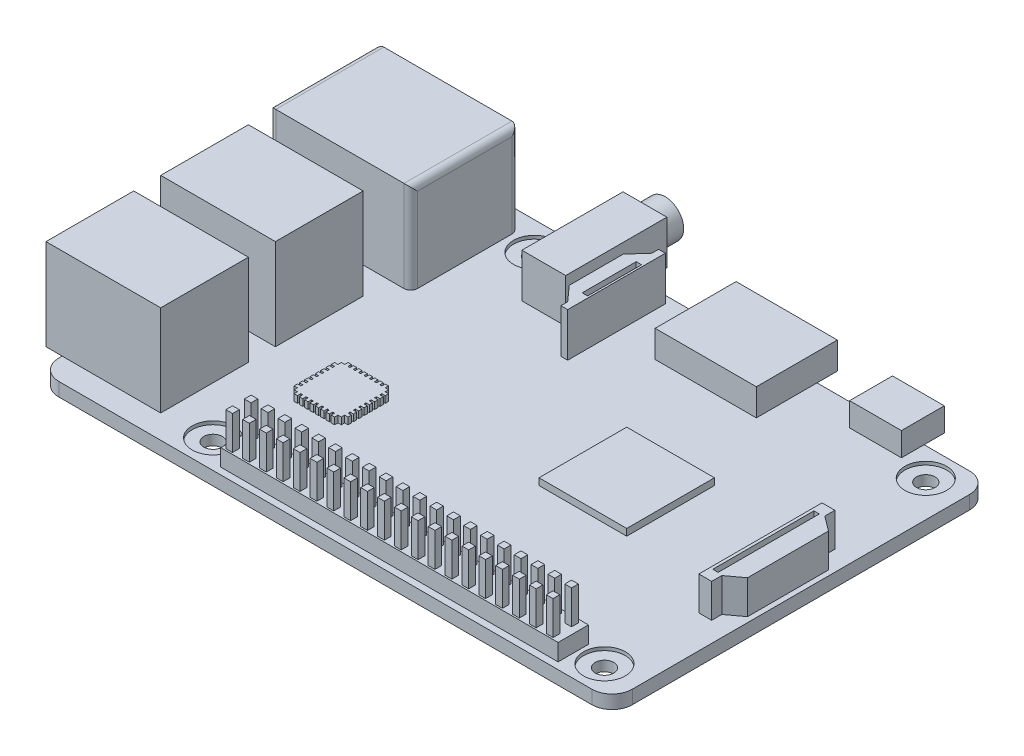
SolidWorks part; units mm, degrees
ref_plane "Alzado" through (0, 0, 0) normal (0, 0, 1) x (1, 0, 0)
ref_plane "Planta" through (0, 0, 0) normal (0, 1, 0) x (1, 0, 0)
ref_plane "Vista lateral" through (0, 0, 0) normal (1, 0, 0) x (0, 0, -1)
sketch "Sketch3" plane through (0, 0, 0) normal (0, 1, 0) x (1, 0, 0)
  line L1 (-42.5, -28) -> (42.5, -28)
  line L2 (-42.5, -28) -> (-42.5, 28)
  line L3 (-42.5, 28) -> (42.5, 28)
  line L4 (42.5, -28) -> (42.5, 28)
  line L5 (-42.5, -28) -> (42.5, 28) construction
  line L6 (-42.5, 28) -> (42.5, -28) construction
  point P0 (0, 0)
  dimension "D1" = 85
  dimension "D2" = 56
extrude "Boss-Extrude1" add sketch "Sketch3" along normal blind 2
fillet "Fillet1" radius 3 4 edges at (42.5, 1, -28) (-42.5, 1, -28) (-42.5, 1, 28) (42.5, 1, 28)
sketch "Sketch4" plane through (0, 2, 0) normal (0, 1, 0) x (1, 0, 0)
  line L0 (-42.5, 0) -> (42.5, 0) construction
  line L1 (-42.5, 25) -> (-42.5, -25) construction
  line L2 (42.5, -25) -> (42.5, 25) construction
  circle A0 centre (37.1829, -23.8123) radius 3.1
  circle A1 centre (-20.8171, -23.8123) radius 3.1
  circle A2 centre (-20.8171, 23.8123) radius 3.1
  circle A3 centre (37.1829, 23.8123) radius 3.1
  dimension "D1" = 6.2
  dimension "D2" = 2
extrude "Cut-Extrude1" cut sketch "Sketch4" against normal blind 0.5
sketch "Sketch5" plane through (0, 2, 0) normal (0, 1, 0) x (1, 0, 0)
  line L0 (-42.5, 0) -> (42.5, 0) construction
  line L1 (-42.5, 25) -> (-42.5, -25) construction
  line L2 (42.5, -25) -> (42.5, 25) construction
  circle A0 centre (37.1829, 23.8123) radius 1.375
  circle A1 centre (-20.8171, 23.8123) radius 1.375
  circle A2 centre (37.1829, -23.8123) radius 1.375
  circle A3 centre (-20.8171, -23.8123) radius 1.375
  dimension "D1" = 2.75
  dimension "D2" = 2
extrude "Cut-Extrude2" cut sketch "Sketch5" against normal through all
sketch "Sketch7" plane through (0, 2, 0) normal (0, 1, 0) x (1, 0, 0)
  line L0 (39.5, 28) -> (-39.5, 28) construction
  line L1 (-45.8342, 25.5) -> (-24.8342, 25.5)
  line L2 (-45.8342, 25.5) -> (-45.8342, 9.5)
  line L3 (-45.8342, 9.5) -> (-24.8342, 9.5)
  line L4 (-24.8342, 25.5) -> (-24.8342, 9.5)
  dimension "D1" = 16
  dimension "D2" = 21
  dimension "D3" = 2.5
extrude "Boss-Extrude2" add sketch "Sketch7" along normal blind 13.5
fillet "Fillet2" radius 1 6 edges at (-45.8342, 8.75, -9.5) (-45.8342, 8.75, -25.5) (-24.8342, 8.75, -9.5) (-24.8342, 8.75, -25.5) (-24.8342, 15.5, -17.5) (-45.8342, 15.5, -17.5)
sketch "Sketch8" plane through (-45.8342, 0, 0) normal (-1, 0, 0) x (0, 0, 1)
  line L0 (-19.75, 2.5) -> (-15.25, 2.5)
  line L1 (-15.25, 2.5) -> (-15.25, 4)
  line L2 (-15.25, 4) -> (-13.25, 4)
  line L3 (-13.25, 4) -> (-13.25, 5.5)
  line L4 (-13.25, 5.5) -> (-11.25, 5.5)
  line L5 (-11.25, 5.5) -> (-11.25, 13)
  line L7 (-19.75, 2.5) -> (-19.75, 4)
  line L8 (-19.75, 4) -> (-21.75, 4)
  line L9 (-21.75, 4) -> (-21.75, 5.5)
  line L10 (-21.75, 5.5) -> (-23.75, 5.5)
  line L11 (-23.75, 5.5) -> (-23.75, 13)
  line L12 (-24.5, 2) -> (-10.5, 2) construction
  line L13 (-23.75, 13) -> (-11.25, 13)
  point P2 (-11.277, 13)
  point P18 (-17.5, 2)
  dimension "D1" = 4.5
  dimension "D2" = 1.5
  dimension "D3" = 2
  dimension "D4" = 1.5
  dimension "D5" = 2
  dimension "D6" = 7.5
  dimension "D7" = 0.5
extrude "Cut-Extrude4" cut sketch "Sketch8" against normal blind 13.5
sketch "Sketch9" plane through (0, 2, 0) normal (0, 1, 0) x (1, 0, 0)
  line L0 (39.5, 28) -> (-39.5, 28) construction
  line L1 (-44.8961, 5.5) -> (-27.8961, 5.5)
  line L2 (-44.8961, 5.5) -> (-44.8961, -7.5)
  line L3 (-44.8961, -7.5) -> (-27.8961, -7.5)
  line L4 (-27.8961, 5.5) -> (-27.8961, -7.5)
  point P6 (-44.8961, -1)
  dimension "D1" = 29
  dimension "D2" = 13
  dimension "D3" = 17
extrude "Boss-Extrude3" add sketch "Sketch9" along normal blind 13.5
sketch "Sketch10" plane through (-44.8961, 0, 0) normal (-1, 0, 0) x (0, 0, 1)
  line L0 (-5.5, 2) -> (7.5, 2) construction
  line L1 (7.5, 15.5) -> (7.5, 2) construction
  line L2 (-4.3, 14.2948) -> (6.3, 14.2948)
  line L3 (-4.3, 14.2948) -> (-4.3, 9.2948)
  line L4 (-4.3, 9.2948) -> (6.3, 9.2948)
  line L5 (6.3, 14.2948) -> (6.3, 9.2948)
  line L6 (-4.3, 14.2948) -> (6.3, 9.2948) construction
  line L7 (-4.3, 9.2948) -> (6.3, 14.2948) construction
  line L8 (-4.3919, 7.9541) -> (6.2081, 7.9541)
  line L9 (-4.3919, 7.9541) -> (-4.3919, 2.9541)
  line L10 (-4.3919, 2.9541) -> (6.2081, 2.9541)
  line L11 (6.2081, 7.9541) -> (6.2081, 2.9541)
  line L12 (-4.3919, 7.9541) -> (6.2081, 2.9541) construction
  line L13 (-4.3919, 2.9541) -> (6.2081, 7.9541) construction
  point P2 (1, 11.7948)
  point P9 (0.9081, 5.4541)
  point P14 (1, 4.59)
  point P15 (1.0081, 4.5341)
  point P16 (1.0081, 4.9421)
  point P17 (1.0081, 5.4541)
  dimension "D1" = 5
  dimension "D2" = 5
  dimension "D3" = 10.6
  dimension "D4" = 10.6
  dimension "D5" = 1.2
  dimension "D6" = 1.2919
extrude "Cut-Extrude5" cut sketch "Sketch10" against normal blind 13.5
sketch "Sketch11" plane through (-31.3961, 0, 0) normal (-1, 0, 0) x (0, 0, 1)
  line L0 (6.3, 14.2948) -> (-4.3, 14.2948) construction
  line L1 (-3.7, 13.5448) -> (5.7, 13.5448)
  line L2 (-3.7, 13.5448) -> (-3.7, 12.7448)
  line L3 (-3.7, 12.7448) -> (5.7, 12.7448)
  line L4 (5.7, 13.5448) -> (5.7, 12.7448)
  line L5 (-3.7919, 7.2041) -> (5.6081, 7.2041)
  line L6 (-3.7919, 7.2041) -> (-3.7919, 6.4041)
  line L7 (-3.7919, 6.4041) -> (5.6081, 6.4041)
  line L8 (5.6081, 7.2041) -> (5.6081, 6.4041)
  line L9 (6.2081, 7.9541) -> (-4.3919, 7.9541) construction
  line L10 (-4.3919, 7.9541) -> (-4.3919, 2.9541) construction
  line L11 (6.2081, 2.9541) -> (6.2081, 7.9541) construction
  line L12 (6.3, 9.2948) -> (6.3, 14.2948) construction
  line L13 (-4.3, 14.2948) -> (-4.3, 9.2948) construction
  line L14 (-4.3, 9.2948) -> (6.3, 9.2948) construction
  dimension "D1" = 0.8
  dimension "D2" = 0.8
  dimension "D3" = 0.75
  dimension "D4" = 0.75
  dimension "D5" = 0.6
  dimension "D6" = 0.6
  dimension "D7" = 0.6
  dimension "D8" = 0.6
extrude "Boss-Extrude4" add sketch "Sketch11" along normal blind 13.5
pattern_linear "LPattern2" count 2 spacing 17 along (0, 0, 1) of "Boss-Extrude3", "Boss-Extrude4"
sketch "Sketch15" plane through (-44.8961, 0, 0) normal (-1, 0, 0) x (0, 0, 1)
  line L1 (12.7, 14.29) -> (23.3, 14.29)
  line L2 (12.7, 14.29) -> (12.7, 9.29)
  line L3 (12.7, 9.29) -> (23.3, 9.29)
  line L4 (23.3, 14.29) -> (23.3, 9.29)
  line L5 (12.7, 7.8125) -> (23.3, 7.8125)
  line L6 (12.7, 7.8125) -> (12.7, 2.8125)
  line L7 (12.7, 2.8125) -> (23.3, 2.8125)
  line L8 (23.3, 7.8125) -> (23.3, 2.8125)
  line L9 (24.5, 15.5) -> (24.5, 2) construction
  line L11 (11.5, 15.5) -> (24.5, 15.5) construction
  dimension "D1" = 5
  dimension "D2" = 5
  dimension "D3" = 5
  dimension "D4" = 1.2
  dimension "D5" = 10.6
  dimension "D6" = 1.2
  dimension "D7" = 10.6
  dimension "D8" = 1.21
extrude "Cut-Extrude6" cut sketch "Sketch15" against normal blind 13.5
sketch "Sketch16" plane through (-31.3961, 0, 0) normal (-1, 0, 0) x (0, 0, 1)
  line L3 (13.3, 13.54) -> (22.7, 13.54)
  line L4 (13.3, 13.54) -> (13.3, 12.74)
  line L5 (13.3, 12.74) -> (22.7, 12.74)
  line L6 (22.7, 13.54) -> (22.7, 12.74)
  line L7 (23.3, 14.29) -> (12.7, 14.29) construction
  line L8 (23.3, 7.8125) -> (12.7, 7.8125) construction
  line L9 (13.3, 7.0625) -> (22.7, 7.0625)
  line L10 (13.3, 7.0625) -> (13.3, 6.2625)
  line L11 (13.3, 6.2625) -> (22.7, 6.2625)
  line L12 (22.7, 7.0625) -> (22.7, 6.2625)
  line L15 (12.7, 14.29) -> (12.7, 9.29) construction
  line L16 (23.3, 9.29) -> (23.3, 14.29) construction
  line L17 (23.3, 2.8125) -> (23.3, 7.8125) construction
  dimension "D1" = 0.8
  dimension "D2" = 9.4
  dimension "D3" = 0.75
  dimension "D4" = 9.4
  dimension "D5" = 0.8
  dimension "D6" = 0.75
  dimension "D7" = 0.6
  dimension "D8" = 0.6
  dimension "D9" = 0.6
extrude "Boss-Extrude5" add sketch "Sketch16" along normal blind 13.5
sketch "Sketch18" plane through (0, 2, 0) normal (0, 1, 0) x (1, 0, 0)
  line L0 (42.5, -25) -> (42.5, 25) construction
  line L1 (-16.5, -22.5) -> (33.5, -22.5)
  line L2 (-16.5, -22.5) -> (-16.5, -27)
  line L3 (-16.5, -27) -> (33.5, -27)
  line L4 (33.5, -22.5) -> (33.5, -27)
  line L5 (-16.5, -22.5) -> (33.5, -27) construction
  line L6 (-16.5, -27) -> (33.5, -22.5) construction
  line L7 (-39.5, -28) -> (39.5, -28) construction
  point P0 (8.5, -24.75)
  point P9 (0, 0)
  point P10 (10.5, -24.75)
  point P11 (10.5, -24.75)
  point P12 (10.5, -24.75)
  dimension "D1" = 34
  dimension "D2" = 4.5
  dimension "D3" = 1
  dimension "D4" = 50
extrude "Boss-Extrude6" add sketch "Sketch18" along normal blind 2.5
sketch "Sketch19" plane through (0, 4.5, 0) normal (0, 1, 0) x (1, 0, 0)
  line L0 (-16.5, -22.5) -> (-16.5, -27) construction
  line L1 (-16, -25.75) -> (-15, -25.75)
  line L2 (-16, -25.75) -> (-16, -26.75)
  line L3 (-16, -26.75) -> (-15, -26.75)
  line L4 (-15, -25.75) -> (-15, -26.75)
  line L5 (-16, -25.75) -> (-15, -26.75) construction
  line L6 (-16, -26.75) -> (-15, -25.75) construction
  line L7 (-16, -25.75) -> (-16.5, -25.75)
  line L8 (-16.5, -27) -> (33.5, -27) construction
  line L9 (-13.5, -25.75) -> (-12.5, -25.75)
  line L10 (-12.5, -25.75) -> (-12.5, -26.75)
  line L11 (-13.5, -26.75) -> (-12.5, -26.75)
  line L12 (-13.5, -25.75) -> (-13.5, -26.75)
  line L13 (-11, -25.75) -> (-10, -25.75)
  line L14 (-10, -25.75) -> (-10, -26.75)
  line L15 (-11, -26.75) -> (-10, -26.75)
  line L16 (-11, -25.75) -> (-11, -26.75)
  line L17 (-8.5, -25.75) -> (-7.5, -25.75)
  line L18 (-7.5, -25.75) -> (-7.5, -26.75)
  line L19 (-8.5, -26.75) -> (-7.5, -26.75)
  line L20 (-8.5, -25.75) -> (-8.5, -26.75)
  line L21 (-6, -25.75) -> (-5, -25.75)
  line L22 (-5, -25.75) -> (-5, -26.75)
  line L23 (-6, -26.75) -> (-5, -26.75)
  line L24 (-6, -25.75) -> (-6, -26.75)
  line L25 (-3.5, -25.75) -> (-2.5, -25.75)
  line L26 (-2.5, -25.75) -> (-2.5, -26.75)
  line L27 (-3.5, -26.75) -> (-2.5, -26.75)
  line L28 (-3.5, -25.75) -> (-3.5, -26.75)
  line L29 (-1, -25.75) -> (0, -25.75)
  line L30 (0, -25.75) -> (0, -26.75)
  line L31 (-1, -26.75) -> (0, -26.75)
  line L32 (-1, -25.75) -> (-1, -26.75)
  line L33 (1.5, -25.75) -> (2.5, -25.75)
  line L34 (2.5, -25.75) -> (2.5, -26.75)
  line L35 (1.5, -26.75) -> (2.5, -26.75)
  line L36 (1.5, -25.75) -> (1.5, -26.75)
  line L37 (4, -25.75) -> (5, -25.75)
  line L38 (5, -25.75) -> (5, -26.75)
  line L39 (4, -26.75) -> (5, -26.75)
  line L40 (4, -25.75) -> (4, -26.75)
  line L41 (6.5, -25.75) -> (7.5, -25.75)
  line L42 (7.5, -25.75) -> (7.5, -26.75)
  line L43 (6.5, -26.75) -> (7.5, -26.75)
  line L44 (6.5, -25.75) -> (6.5, -26.75)
  line L45 (9, -25.75) -> (10, -25.75)
  line L46 (10, -25.75) -> (10, -26.75)
  line L47 (9, -26.75) -> (10, -26.75)
  line L48 (9, -25.75) -> (9, -26.75)
  line L49 (11.5, -25.75) -> (12.5, -25.75)
  line L50 (12.5, -25.75) -> (12.5, -26.75)
  line L51 (11.5, -26.75) -> (12.5, -26.75)
  line L52 (11.5, -25.75) -> (11.5, -26.75)
  line L53 (14, -25.75) -> (15, -25.75)
  line L54 (15, -25.75) -> (15, -26.75)
  line L55 (14, -26.75) -> (15, -26.75)
  line L56 (14, -25.75) -> (14, -26.75)
  line L57 (16.5, -25.75) -> (17.5, -25.75)
  line L58 (17.5, -25.75) -> (17.5, -26.75)
  line L59 (16.5, -26.75) -> (17.5, -26.75)
  line L60 (16.5, -25.75) -> (16.5, -26.75)
  line L61 (19, -25.75) -> (20, -25.75)
  line L62 (20, -25.75) -> (20, -26.75)
  line L63 (19, -26.75) -> (20, -26.75)
  line L64 (19, -25.75) -> (19, -26.75)
  line L65 (21.5, -25.75) -> (22.5, -25.75)
  line L66 (22.5, -25.75) -> (22.5, -26.75)
  line L67 (21.5, -26.75) -> (22.5, -26.75)
  line L68 (21.5, -25.75) -> (21.5, -26.75)
  line L69 (24, -25.75) -> (25, -25.75)
  line L70 (25, -25.75) -> (25, -26.75)
  line L71 (24, -26.75) -> (25, -26.75)
  line L72 (24, -25.75) -> (24, -26.75)
  line L73 (26.5, -25.75) -> (27.5, -25.75)
  line L74 (27.5, -25.75) -> (27.5, -26.75)
  line L75 (26.5, -26.75) -> (27.5, -26.75)
  line L76 (26.5, -25.75) -> (26.5, -26.75)
  line L77 (29, -25.75) -> (30, -25.75)
  line L78 (30, -25.75) -> (30, -26.75)
  line L79 (29, -26.75) -> (30, -26.75)
  line L80 (29, -25.75) -> (29, -26.75)
  line L81 (31.5, -25.75) -> (32.5, -25.75)
  line L82 (32.5, -25.75) -> (32.5, -26.75)
  line L83 (31.5, -26.75) -> (32.5, -26.75)
  line L84 (31.5, -25.75) -> (31.5, -26.75)
  point P0 (-15.5, -26.25)
  dimension "D1" = 1
  dimension "D2" = 1
  dimension "D3" = 0.5
  dimension "D4" = 0.25
  dimension "D5" = 20
extrude "Cut-Extrude7" cut sketch "Sketch19" against normal up to vertex (2.5 mm away) contours L4 L1 L2 L3 | L9 L12 L11 L10 | L13 L16 L15 L14 | L81 L84 L83 L82 | L77 L80 L79 L78 | L73 L76 L75 L74 | L57 L60 L59 L58 | L53 L56 L55 L54 | L17 L20 L19 L18 | L29 L32 L31 L30 | L41 L44 L43 L42 | L61 L64 L63 L62 | L72 L71 L70 L69 | L68 L67 L66 L65 | L52 L51 L50 L49 | L48 L47 L46 L45 | L39 L38 L37 L40 | L34 L35 L36 L33 | L23 L22 L21 L24 | L26 L27 L28 L25 region at (-15.5, 4.5, 26.25) region at (-13, 4.5, 26.25) region at (-10.5, 4.5, 26.25) region at (-8, 4.5, 26.25) region at (-0.5, 4.5, 26.25) region at (7, 4.5, 26.25) region at (14.5, 4.5, 26.25) region at (17, 4.5, 26.25) region at (19.5, 4.5, 26.25) region at (27, 4.5, 26.25) region at (29.5, 4.5, 26.25) region at (32, 4.5, 26.25) up to point (-16.5, 2, 27)
pattern_linear "LPattern4" count 2 spacing 2.75 along (0, 0, -1) of "Cut-Extrude7"
sketch "Sketch22" plane through (0, 2, 0) normal (0, 1, 0) x (1, 0, 0)
  line L0 (-13.5, -25.75) -> (-13.5, -26.75)
  line L1 (-16, -25.75) -> (-15, -25.75)
  line L2 (-16, -25.75) -> (-16, -26.75)
  line L3 (-16, -26.75) -> (-15, -26.75)
  line L4 (-15, -25.75) -> (-15, -26.75)
  line L5 (-13.5, -25.75) -> (-12.5, -25.75)
  line L6 (-12.5, -25.75) -> (-12.5, -26.75)
  line L7 (-13.5, -26.75) -> (-12.5, -26.75)
  line L8 (-11, -25.75) -> (-11, -26.75)
  line L9 (-11, -25.75) -> (-10, -25.75)
  line L10 (-10, -25.75) -> (-10, -26.75)
  line L11 (-11, -26.75) -> (-10, -26.75)
  line L12 (-8.5, -25.75) -> (-8.5, -26.75)
  line L13 (-8.5, -25.75) -> (-7.5, -25.75)
  line L14 (-7.5, -25.75) -> (-7.5, -26.75)
  line L15 (-8.5, -26.75) -> (-7.5, -26.75)
  line L16 (-6, -25.75) -> (-6, -26.75)
  line L17 (-6, -25.75) -> (-5, -25.75)
  line L18 (-5, -25.75) -> (-5, -26.75)
  line L19 (-6, -26.75) -> (-5, -26.75)
  line L20 (-3.5, -25.75) -> (-3.5, -26.75)
  line L21 (-3.5, -25.75) -> (-2.5, -25.75)
  line L22 (-2.5, -25.75) -> (-2.5, -26.75)
  line L23 (-3.5, -26.75) -> (-2.5, -26.75)
  line L24 (-1, -25.75) -> (-1, -26.75)
  line L25 (-1, -25.75) -> (0, -25.75)
  line L26 (0, -25.75) -> (0, -26.75)
  line L27 (-1, -26.75) -> (0, -26.75)
  line L28 (1.5, -25.75) -> (1.5, -26.75)
  line L29 (1.5, -25.75) -> (2.5, -25.75)
  line L30 (2.5, -25.75) -> (2.5, -26.75)
  line L31 (1.5, -26.75) -> (2.5, -26.75)
  line L32 (4, -25.75) -> (4, -26.75)
  line L33 (4, -25.75) -> (5, -25.75)
  line L34 (5, -25.75) -> (5, -26.75)
  line L35 (4, -26.75) -> (5, -26.75)
  line L36 (6.5, -25.75) -> (6.5, -26.75)
  line L37 (6.5, -25.75) -> (7.5, -25.75)
  line L38 (7.5, -25.75) -> (7.5, -26.75)
  line L39 (6.5, -26.75) -> (7.5, -26.75)
  line L40 (9, -25.75) -> (9, -26.75)
  line L41 (9, -25.75) -> (10, -25.75)
  line L42 (10, -25.75) -> (10, -26.75)
  line L43 (9, -26.75) -> (10, -26.75)
  line L44 (11.5, -25.75) -> (11.5, -26.75)
  line L45 (11.5, -25.75) -> (12.5, -25.75)
  line L46 (12.5, -25.75) -> (12.5, -26.75)
  line L47 (11.5, -26.75) -> (12.5, -26.75)
  line L48 (14, -25.75) -> (14, -26.75)
  line L49 (14, -25.75) -> (15, -25.75)
  line L50 (15, -25.75) -> (15, -26.75)
  line L51 (14, -26.75) -> (15, -26.75)
  line L52 (16.5, -25.75) -> (16.5, -26.75)
  line L53 (16.5, -25.75) -> (17.5, -25.75)
  line L54 (17.5, -25.75) -> (17.5, -26.75)
  line L55 (16.5, -26.75) -> (17.5, -26.75)
  line L56 (19, -25.75) -> (19, -26.75)
  line L57 (19, -25.75) -> (20, -25.75)
  line L58 (20, -25.75) -> (20, -26.75)
  line L59 (19, -26.75) -> (20, -26.75)
  line L60 (21.5, -25.75) -> (21.5, -26.75)
  line L61 (21.5, -25.75) -> (22.5, -25.75)
  line L62 (22.5, -25.75) -> (22.5, -26.75)
  line L63 (21.5, -26.75) -> (22.5, -26.75)
  line L64 (24, -25.75) -> (24, -26.75)
  line L65 (24, -25.75) -> (25, -25.75)
  line L66 (25, -25.75) -> (25, -26.75)
  line L67 (24, -26.75) -> (25, -26.75)
  line L68 (26.5, -25.75) -> (26.5, -26.75)
  line L69 (26.5, -25.75) -> (27.5, -25.75)
  line L70 (27.5, -25.75) -> (27.5, -26.75)
  line L71 (26.5, -26.75) -> (27.5, -26.75)
  line L72 (29, -25.75) -> (29, -26.75)
  line L73 (29, -25.75) -> (30, -25.75)
  line L74 (30, -25.75) -> (30, -26.75)
  line L75 (29, -26.75) -> (30, -26.75)
  line L76 (31.5, -25.75) -> (31.5, -26.75)
  line L77 (31.5, -25.75) -> (32.5, -25.75)
  line L78 (32.5, -25.75) -> (32.5, -26.75)
  line L79 (31.5, -26.75) -> (32.5, -26.75)
  dimension "D1" = 20
extrude "Boss-Extrude7" add sketch "Sketch22" along normal offset from surface (7.5 mm away) 5 up to face at (-5.5, 4.5, 23.5) offset beyond the face yes
pattern_linear "LPattern5" count 2 spacing 2.75 along (0, 0, -1) of "Boss-Extrude7"
sketch "Sketch23" plane through (0, 2, 0) normal (0, 1, 0) x (1, 0, 0)
  line L1 (9.452, 7.2198) -> (22.452, 7.2198)
  line L2 (9.452, 7.2198) -> (9.452, -5.7802)
  line L3 (9.452, -5.7802) -> (22.452, -5.7802)
  line L4 (22.452, 7.2198) -> (22.452, -5.7802)
  dimension "D1" = 13
  dimension "D2" = 13
extrude "Boss-Extrude8" add sketch "Sketch23" along normal blind 1
sketch "Sketch24" plane through (0, 2, 0) normal (0, 1, 0) x (1, 0, 0)
  line L1 (-19.9926, -5.6336) -> (-12.9926, -5.6336)
  line L2 (-19.9926, -5.6336) -> (-19.9926, -12.6336)
  line L3 (-19.9926, -12.6336) -> (-12.9926, -12.6336)
  line L4 (-12.9926, -5.6336) -> (-12.9926, -12.6336)
  line L5 (-19.9926, -5.6336) -> (-12.9926, -12.6336) construction
  line L6 (-19.9926, -12.6336) -> (-12.9926, -5.6336) construction
  point P0 (-16.4926, -9.1336)
  point P5 (-15.3454, -6.6626)
  point P6 (-16.4926, -9.1336)
  dimension "D1" = 7
  dimension "D2" = 7
extrude "Boss-Extrude9" add sketch "Sketch24" along normal blind 1
sketch "Sketch25" plane through (0, 2, 0) normal (0, 1, 0) x (1, 0, 0)
  line L0 (37.6442, 7.9733) -> (39.5442, 7.9733)
  line L1 (39.5442, 7.9733) -> (39.5442, 6.4733)
  line L2 (39.5442, 6.4733) -> (41.7364, 4.8463)
  line L3 (41.7364, 4.8463) -> (41.7364, -7.1537)
  line L4 (41.7364, -7.1537) -> (39.5442, -8.7808)
  line L5 (39.5442, -8.7808) -> (39.5442, -10.2808)
  line L6 (39.5442, -10.2808) -> (37.6442, -10.2808)
  line L7 (37.6442, -10.2808) -> (37.6442, 7.9733)
  dimension "D1" = 12
  dimension "D2" = 1.5
  dimension "D3" = 1.5
  dimension "D4" = 2.73
  dimension "D5" = 1.9
  dimension "D6" = 1.9
  dimension "D7" = 2.73
extrude "Boss-Extrude10" add sketch "Sketch25" along normal blind 5
sketch "Sketch26" plane through (0, 7, 0) normal (0, 1, 0) x (1, 0, 0)
  line L1 (38.0707, -8.6485) -> (38.8707, -8.6485)
  line L2 (38.0707, -8.6485) -> (38.0707, 6.3411)
  line L3 (38.0707, 6.3411) -> (38.8707, 6.3411)
  line L4 (38.8707, -8.6485) -> (38.8707, 6.3411)
  line L5 (38.0707, -8.6485) -> (38.8707, 6.3411) construction
  line L6 (38.0707, 6.3411) -> (38.8707, -8.6485) construction
  point P0 (38.4707, -1.1537)
  dimension "D1" = 0.8
extrude "Cut-Extrude8" cut sketch "Sketch26" against normal blind 5
sketch "Sketch27" plane through (0, 2, 0) normal (0, 1, 0) x (1, 0, 0)
  line L1 (-15.5289, 31.6491) -> (-9.0289, 31.6491)
  line L2 (-15.5289, 31.6491) -> (-15.5289, 16.6575)
  line L3 (-15.5289, 16.6575) -> (-9.0289, 16.6575)
  line L4 (-9.0289, 31.6491) -> (-9.0289, 16.6575)
  line L5 (-15.5289, 31.6491) -> (-9.0289, 16.6575) construction
  line L6 (-15.5289, 16.6575) -> (-9.0289, 31.6491) construction
  point P0 (-12.2789, 24.1533)
  point P5 (-13.3122, 24.1533)
  dimension "D1" = 6.5
extrude "Boss-Extrude11" add sketch "Sketch27" along normal blind 6.5
sketch "Sketch28" plane through (0, 0, -31.6491) normal (0, 0, -1) x (-1, 0, 0)
  line L0 (12.2789, 8.5) -> (12.2789, 2) construction
  line L1 (9.0289, 8.5) -> (15.5289, 8.5) construction
  line L2 (9.0289, 2) -> (15.5289, 2) construction
  circle A0 centre (12.2789, 5.25) radius 2.75
  dimension "D1" = 5.5
extrude "Boss-Extrude12" add sketch "Sketch28" along normal blind 3
sketch "Sketch29" plane through (0, 0, -34.6491) normal (0, 0, -1) x (-1, 0, 0)
  circle A0 centre (12.2789, 5.25) radius 1.5
  circle A1 centre (12.2789, 5.25) radius 2.75 construction
  dimension "D1" = 3
extrude "Cut-Extrude10" cut sketch "Sketch29" against normal blind 15
sketch "Sketch30" plane through (0, 2, 0) normal (0, 1, 0) x (1, 0, 0)
  line L2 (-7.5086, 15.6647) -> (-7.5086, 23.6647)
  line L3 (-7.5086, 23.6647) -> (-5.5086, 25.9007)
  line L4 (-5.5086, 25.9007) -> (-5.5086, 26.9007)
  line L5 (-5.5086, 26.9007) -> (-4.5086, 26.9007)
  line L8 (-7.5086, 19.6647) -> (-2.3328, 19.6647) construction
  line L9 (-5.5086, 13.4286) -> (-5.5086, 12.4286)
  line L10 (-5.5086, 12.4286) -> (-4.5086, 12.4286)
  line L11 (-7.5086, 15.6647) -> (-5.5086, 13.4286)
  line L12 (-4.5086, 26.9007) -> (-4.5086, 12.4286)
  point P0 (-4.5294, 12.3726)
  dimension "D1" = 3
  dimension "D2" = 3
  dimension "D3" = 1
  dimension "D5" = 4
  dimension "D6" = 1
extrude "Boss-Extrude13" add sketch "Sketch30" along normal blind 6.5
sketch "Sketch31" plane through (0, 8.5, 0) normal (0, 1, 0) x (1, 0, 0)
  line L1 (-5.5863, 15.6647) -> (-4.7863, 15.6647)
  line L2 (-5.5863, 15.6647) -> (-5.5863, 23.6647)
  line L3 (-5.5863, 23.6647) -> (-4.7863, 23.6647)
  line L4 (-4.7863, 15.6647) -> (-4.7863, 23.6647)
  line L5 (-5.5863, 15.6647) -> (-4.7863, 23.6647) construction
  line L6 (-5.5863, 23.6647) -> (-4.7863, 15.6647) construction
  line L7 (-7.5086, 23.6647) -> (-4.5086, 23.6647)
  line L9 (-4.5086, 12.4286) -> (-4.5086, 26.9007) construction
  point P0 (-5.1863, 19.6647)
  dimension "D1" = 0.8
  dimension "D2" = 8
extrude "Cut-Extrude11" cut sketch "Sketch31" against normal blind 6.5 contours L1 L4 L3 L2 region at (-5.1863, 8.5, -19.6647)
sketch "Sketch32" plane through (0, 2, 0) normal (0, 1, 0) x (1, 0, 0)
  line L1 (1.8732, 31.0095) -> (16.8732, 31.0095)
  line L2 (1.8732, 31.0095) -> (1.8732, 19.0095)
  line L3 (1.8732, 19.0095) -> (16.8732, 19.0095)
  line L4 (16.8732, 31.0095) -> (16.8732, 19.0095)
  line L5 (1.8732, 31.0095) -> (16.8732, 19.0095) construction
  line L6 (1.8732, 19.0095) -> (16.8732, 31.0095) construction
  point P0 (9.3732, 25.0095)
  point P5 (9.3638, 19.7826)
  point P6 (9.3732, 25.0095)
  dimension "D1" = 12
  dimension "D2" = 15
extrude "Boss-Extrude14" add sketch "Sketch32" along normal blind 4
sketch "Sketch34" plane through (0, 0, -31.0095) normal (0, 0, -1) x (-1, 0, 0)
  line L0 (-15.8732, 5.4336) -> (-2.8732, 5.4336)
  line L1 (-2.8732, 5.4336) -> (-2.8732, 2.9336)
  line L3 (-4.8924, 2.2264) -> (-14.1924, 2.2264)
  line L5 (-15.8732, 2.9336) -> (-15.8732, 5.4336)
  line L6 (-15.8732, 2.9336) -> (-14.5732, 2.9336)
  line L7 (-14.5732, 2.9336) -> (-14.1924, 2.2264)
  line L8 (-4.8924, 2.2264) -> (-4.1732, 2.9336)
  line L9 (-4.1732, 2.9336) -> (-2.8732, 2.9336)
  line L10 (-1.8732, 6) -> (-1.8732, 2) construction
  dimension "D1" = 2.5
  dimension "D2" = 2.5
  dimension "D3" = 1.3
  dimension "D4" = 1.3
  dimension "D5" = 9.3
  dimension "D6" = 13
  dimension "D7" = 1
extrude "Cut-Extrude13" cut sketch "Sketch34" against normal blind 11
sketch "Sketch35" plane through (0, 0, -20.0095) normal (0, 0, -1) x (-1, 0, 0)
  line L0 (-2.8732, 5.4336) -> (-15.8732, 5.4336) construction
  line L1 (-15.4732, 4.7336) -> (-3.2732, 4.7336)
  line L2 (-15.4732, 4.7336) -> (-15.4732, 4.0336)
  line L3 (-15.4732, 4.0336) -> (-3.2732, 4.0336)
  line L4 (-3.2732, 4.7336) -> (-3.2732, 4.0336)
  line L5 (-15.8732, 5.4336) -> (-15.8732, 2.9336) construction
  line L6 (-2.8732, 2.9336) -> (-2.8732, 5.4336) construction
  dimension "D1" = 0.7
  dimension "D2" = 0.7
  dimension "D3" = 0.4
  dimension "D4" = 0.4
extrude "Boss-Extrude15" add sketch "Sketch35" along normal blind 11
sketch "Sketch36" plane through (0, 2, 0) normal (0, 1, 0) x (1, 0, 0)
  line L1 (25.0717, 30.9899) -> (32.7492, 30.9899)
  line L2 (25.0717, 30.9899) -> (25.0717, 24.6362)
  line L3 (25.0717, 24.6362) -> (32.7492, 24.6362)
  line L4 (32.7492, 30.9899) -> (32.7492, 24.6362)
extrude "Boss-Extrude16" add sketch "Sketch36" along normal blind 3.5
sketch "Sketch37" plane through (0, 0, -30.9899) normal (0, 0, -1) x (-1, 0, 0)
  line L0 (-28.9105, 5.5) -> (-28.9105, 2) construction
  line L1 (-32.7492, 5.5) -> (-25.0717, 5.5) construction
  line L2 (-32.7492, 2) -> (-25.0717, 2) construction
  line L3 (-26.5254, 5) -> (-31.2955, 5)
  line L4 (-31.2955, 5) -> (-32.2485, 4.047)
  line L5 (-32.2485, 4.047) -> (-31.2015, 3)
  line L6 (-31.2015, 3) -> (-26.6194, 3)
  line L7 (-32.7492, 5.5) -> (-32.7492, 2) construction
  line L8 (-32.7492, 2) -> (-25.0717, 2) construction
  line L9 (-25.5724, 4.047) -> (-26.6194, 3)
  line L10 (-26.5254, 5) -> (-25.5724, 4.047)
  point P18 (-28.9105, 3)
  point P20 (-28.9105, 5)
  dimension "D1" = 2
  dimension "D2" = 1
extrude "Cut-Extrude14" cut sketch "Sketch37" against normal blind 6
sketch "Sketch38" plane through (0, 0, -24.9899) normal (0, 0, -1) x (-1, 0, 0)
  line L1 (-31.2955, 4.6333) -> (-26.5254, 4.6333)
  line L2 (-31.2955, 4.6333) -> (-31.2955, 4.1139)
  line L3 (-31.2955, 4.1139) -> (-26.5254, 4.1139)
  line L4 (-26.5254, 4.6333) -> (-26.5254, 4.1139)
extrude "Boss-Extrude17" add sketch "Sketch38" along normal blind 6
sketch "Sketch39" plane through (0, 2, 0) normal (0, 1, 0) x (1, 0, 0)
  line L0 (-12.9926, -5.6336) -> (-19.9926, -5.6336) construction
  line L1 (-19.4926, -5.6336) -> (-18.9926, -5.6336)
  line L2 (-19.4926, -5.6336) -> (-19.4926, -5.1336)
  line L3 (-19.4926, -5.1336) -> (-18.9926, -5.1336)
  line L4 (-18.9926, -5.6336) -> (-18.9926, -5.1336)
  line L5 (-19.9926, -5.6336) -> (-19.9926, -12.6336) construction
  line L6 (-18.7069, -5.1336) -> (-18.2069, -5.1336)
  line L7 (-18.7069, -5.6336) -> (-18.7069, -5.1336)
  line L8 (-18.2069, -5.6336) -> (-18.2069, -5.1336)
  line L9 (-18.7069, -5.6336) -> (-18.2069, -5.6336)
  line L10 (-17.9212, -5.1336) -> (-17.4212, -5.1336)
  line L11 (-17.9212, -5.6336) -> (-17.9212, -5.1336)
  line L12 (-17.4212, -5.6336) -> (-17.4212, -5.1336)
  line L13 (-17.9212, -5.6336) -> (-17.4212, -5.6336)
  line L14 (-17.1354, -5.1336) -> (-16.6354, -5.1336)
  line L15 (-17.1354, -5.6336) -> (-17.1354, -5.1336)
  line L16 (-16.6354, -5.6336) -> (-16.6354, -5.1336)
  line L17 (-17.1354, -5.6336) -> (-16.6354, -5.6336)
  line L18 (-16.3497, -5.1336) -> (-15.8497, -5.1336)
  line L19 (-16.3497, -5.6336) -> (-16.3497, -5.1336)
  line L20 (-15.8497, -5.6336) -> (-15.8497, -5.1336)
  line L21 (-16.3497, -5.6336) -> (-15.8497, -5.6336)
  line L22 (-15.564, -5.1336) -> (-15.064, -5.1336)
  line L23 (-15.564, -5.6336) -> (-15.564, -5.1336)
  line L24 (-15.064, -5.6336) -> (-15.064, -5.1336)
  line L25 (-15.564, -5.6336) -> (-15.064, -5.6336)
  line L26 (-14.7783, -5.1336) -> (-14.2783, -5.1336)
  line L27 (-14.7783, -5.6336) -> (-14.7783, -5.1336)
  line L28 (-14.2783, -5.6336) -> (-14.2783, -5.1336)
  line L29 (-14.7783, -5.6336) -> (-14.2783, -5.6336)
  line L30 (-13.9926, -5.1336) -> (-13.4926, -5.1336)
  line L31 (-13.9926, -5.6336) -> (-13.9926, -5.1336)
  line L32 (-13.4926, -5.6336) -> (-13.4926, -5.1336)
  line L33 (-13.9926, -5.6336) -> (-13.4926, -5.6336)
  line L34 (-12.9926, -12.6336) -> (-12.9926, -5.6336) construction
  line L35 (-19.9926, -9.1336) -> (-12.9926, -9.1336) construction
  line L36 (-12.9926, -12.6336) -> (-12.9926, -5.6336) construction
  line L37 (-14.7783, -12.6336) -> (-14.7783, -13.1336)
  line L38 (-15.064, -12.6336) -> (-15.064, -13.1336)
  line L39 (-16.6354, -12.6336) -> (-16.6354, -13.1336)
  line L40 (-15.564, -12.6336) -> (-15.564, -13.1336)
  line L41 (-15.564, -13.1336) -> (-15.064, -13.1336)
  line L42 (-15.8497, -12.6336) -> (-15.8497, -13.1336)
  line L43 (-16.3497, -12.6336) -> (-16.3497, -13.1336)
  line L44 (-16.3497, -13.1336) -> (-15.8497, -13.1336)
  line L45 (-17.1354, -12.6336) -> (-17.1354, -13.1336)
  line L46 (-17.1354, -13.1336) -> (-16.6354, -13.1336)
  line L47 (-17.4212, -12.6336) -> (-17.4212, -13.1336)
  line L48 (-17.9212, -12.6336) -> (-17.9212, -13.1336)
  line L49 (-17.9212, -13.1336) -> (-17.4212, -13.1336)
  line L50 (-18.2069, -12.6336) -> (-18.2069, -13.1336)
  line L51 (-18.7069, -12.6336) -> (-18.7069, -13.1336)
  line L52 (-18.7069, -13.1336) -> (-18.2069, -13.1336)
  line L53 (-18.9926, -12.6336) -> (-18.9926, -13.1336)
  line L54 (-19.4926, -13.1336) -> (-18.9926, -13.1336)
  line L55 (-19.4926, -12.6336) -> (-19.4926, -13.1336)
  line L56 (-19.4926, -12.6336) -> (-18.9926, -12.6336)
  line L57 (-18.7069, -12.6336) -> (-18.2069, -12.6336)
  line L58 (-17.9212, -12.6336) -> (-17.4212, -12.6336)
  line L59 (-17.1354, -12.6336) -> (-16.6354, -12.6336)
  line L60 (-16.3497, -12.6336) -> (-15.8497, -12.6336)
  line L61 (-15.564, -12.6336) -> (-15.064, -12.6336)
  line L62 (-14.7783, -12.6336) -> (-14.2783, -12.6336)
  line L63 (-13.9926, -12.6336) -> (-13.4926, -12.6336)
  line L64 (-14.2783, -12.6336) -> (-14.2783, -13.1336)
  line L65 (-14.7783, -13.1336) -> (-14.2783, -13.1336)
  line L66 (-13.9926, -13.1336) -> (-13.4926, -13.1336)
  line L67 (-13.9926, -12.6336) -> (-13.9926, -13.1336)
  line L68 (-13.4926, -12.6336) -> (-13.4926, -13.1336)
  line L69 (-19.9926, -5.6336) -> (-19.9926, -12.6336) construction
  line L70 (-19.9926, -6.1336) -> (-20.4926, -6.1336)
  line L71 (-19.9926, -6.1336) -> (-19.9926, -6.6336)
  line L72 (-19.9926, -6.6336) -> (-20.4926, -6.6336)
  line L73 (-20.4926, -6.1336) -> (-20.4926, -6.6336)
  line L74 (-12.9926, -5.6336) -> (-19.9926, -5.6336) construction
  line L75 (-19.9926, -6.9193) -> (-20.4926, -6.9193)
  line L76 (-20.4926, -6.9193) -> (-20.4926, -7.4193)
  line L77 (-19.9926, -7.4193) -> (-20.4926, -7.4193)
  line L78 (-19.9926, -6.9193) -> (-19.9926, -7.4193)
  line L79 (-19.9926, -7.705) -> (-20.4926, -7.705)
  line L80 (-20.4926, -7.705) -> (-20.4926, -8.205)
  line L81 (-19.9926, -8.205) -> (-20.4926, -8.205)
  line L82 (-19.9926, -7.705) -> (-19.9926, -8.205)
  line L83 (-19.9926, -8.4907) -> (-20.4926, -8.4907)
  line L84 (-20.4926, -8.4907) -> (-20.4926, -8.9907)
  line L85 (-19.9926, -8.9907) -> (-20.4926, -8.9907)
  line L86 (-19.9926, -8.4907) -> (-19.9926, -8.9907)
  line L87 (-19.9926, -9.2764) -> (-20.4926, -9.2764)
  line L88 (-20.4926, -9.2764) -> (-20.4926, -9.7764)
  line L89 (-19.9926, -9.7764) -> (-20.4926, -9.7764)
  line L90 (-19.9926, -9.2764) -> (-19.9926, -9.7764)
  line L91 (-19.9926, -10.0621) -> (-20.4926, -10.0621)
  line L92 (-20.4926, -10.0621) -> (-20.4926, -10.5621)
  line L93 (-19.9926, -10.5621) -> (-20.4926, -10.5621)
  line L94 (-19.9926, -10.0621) -> (-19.9926, -10.5621)
  line L95 (-19.9926, -10.8478) -> (-20.4926, -10.8478)
  line L96 (-20.4926, -10.8478) -> (-20.4926, -11.3478)
  line L97 (-19.9926, -11.3478) -> (-20.4926, -11.3478)
  line L98 (-19.9926, -10.8478) -> (-19.9926, -11.3478)
  line L99 (-19.9926, -11.6336) -> (-20.4926, -11.6336)
  line L100 (-20.4926, -11.6336) -> (-20.4926, -12.1336)
  line L101 (-19.9926, -12.1336) -> (-20.4926, -12.1336)
  line L102 (-19.9926, -11.6336) -> (-19.9926, -12.1336)
  line L103 (-19.9926, -12.6336) -> (-12.9926, -12.6336) construction
  line L104 (-16.4926, -5.6336) -> (-16.4926, -12.6336) construction
  line L105 (-12.9926, -6.1336) -> (-12.9926, -6.6336)
  line L106 (-12.4926, -6.1336) -> (-12.4926, -6.6336)
  line L107 (-12.9926, -6.9193) -> (-12.9926, -7.4193)
  line L108 (-12.9926, -7.705) -> (-12.9926, -8.205)
  line L109 (-12.9926, -8.205) -> (-12.4926, -8.205)
  line L110 (-12.4926, -8.4907) -> (-12.4926, -8.9907)
  line L111 (-12.9926, -11.6336) -> (-12.9926, -12.1336)
  line L112 (-12.9926, -12.1336) -> (-12.4926, -12.1336)
  line L113 (-12.4926, -11.6336) -> (-12.4926, -12.1336)
  line L114 (-12.9926, -11.6336) -> (-12.4926, -11.6336)
  line L115 (-12.9926, -10.8478) -> (-12.9926, -11.3478)
  line L116 (-12.9926, -11.3478) -> (-12.4926, -11.3478)
  line L117 (-12.4926, -10.8478) -> (-12.4926, -11.3478)
  line L118 (-12.9926, -10.8478) -> (-12.4926, -10.8478)
  line L119 (-12.9926, -10.0621) -> (-12.9926, -10.5621)
  line L120 (-12.9926, -10.5621) -> (-12.4926, -10.5621)
  line L121 (-12.4926, -10.0621) -> (-12.4926, -10.5621)
  line L122 (-12.9926, -10.0621) -> (-12.4926, -10.0621)
  line L123 (-12.9926, -9.2764) -> (-12.9926, -9.7764)
  line L124 (-12.9926, -9.7764) -> (-12.4926, -9.7764)
  line L125 (-12.4926, -9.2764) -> (-12.4926, -9.7764)
  line L126 (-12.9926, -9.2764) -> (-12.4926, -9.2764)
  line L127 (-12.9926, -8.4907) -> (-12.9926, -8.9907)
  line L128 (-12.9926, -8.9907) -> (-12.4926, -8.9907)
  line L129 (-12.9926, -8.4907) -> (-12.4926, -8.4907)
  line L130 (-12.4926, -7.705) -> (-12.4926, -8.205)
  line L131 (-12.9926, -7.705) -> (-12.4926, -7.705)
  line L132 (-12.9926, -7.4193) -> (-12.4926, -7.4193)
  line L133 (-12.4926, -6.9193) -> (-12.4926, -7.4193)
  line L134 (-12.9926, -6.9193) -> (-12.4926, -6.9193)
  line L135 (-12.9926, -6.6336) -> (-12.4926, -6.6336)
  line L136 (-12.9926, -6.1336) -> (-12.4926, -6.1336)
  dimension "D1" = 0.5
  dimension "D2" = 0.5
  dimension "D3" = 0.5
  dimension "D5" = 0.5
  dimension "D6" = 0.5
  dimension "D7" = 0.5
  dimension "D8" = 0.5
  dimension "D10" = 0.5
  dimension "D11" = 0.5
  dimension "D4" = 8
  dimension "D9" = 8
extrude "Boss-Extrude18" add sketch "Sketch39" along normal up to surface (1 mm away) up to face at (-16.4926, 3, 9.1336)
sketch "Sketch40" plane through (0, 2, 0) normal (0, 1, 0) x (1, 0, 0)
  text T0 "Raspberry pi 5"
